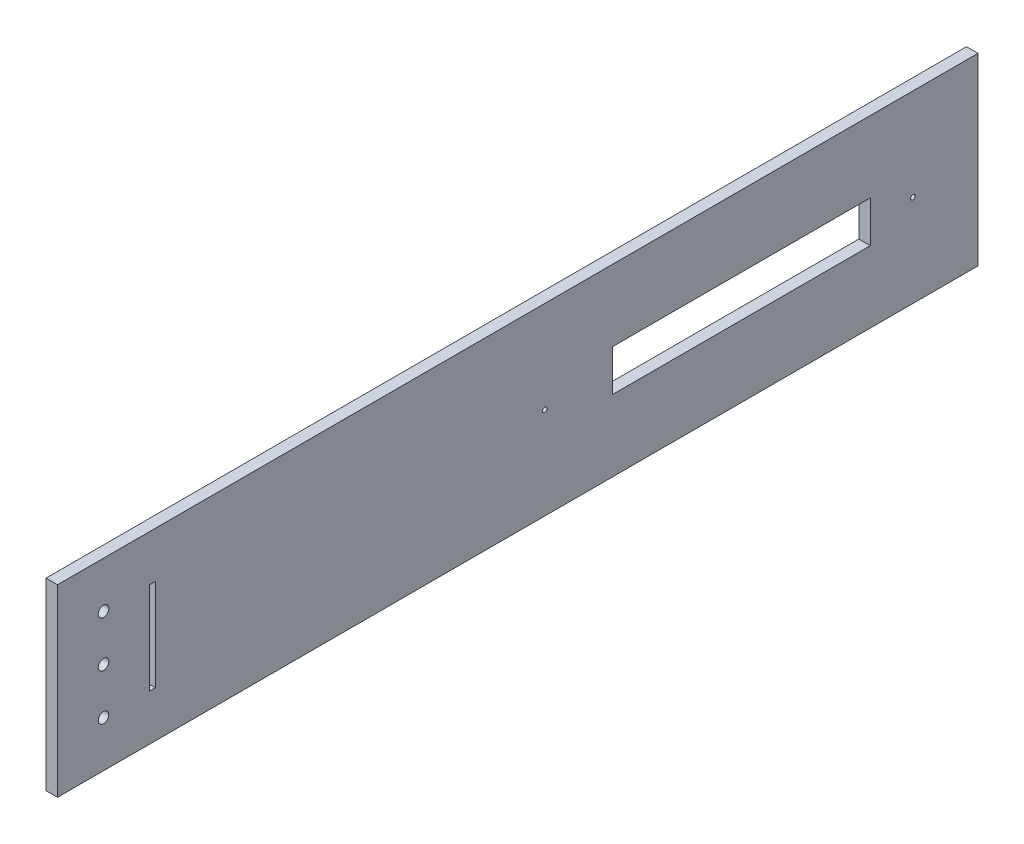
SolidWorks part; units mm, degrees
ref_plane "Front Plane" through (0, 0, 0) normal (0, 0, 1) x (1, 0, 0)
ref_plane "Top Plane" through (0, 0, 0) normal (0, 1, 0) x (1, 0, 0)
ref_plane "Right Plane" through (0, 0, 0) normal (1, 0, 0) x (0, 0, -1)
sketch "Sketch1" plane through (0, 0, 0) normal (1, 0, 0) x (0, 0, -1)
  line L0 (0, 0) -> (-254, 0) construction
  line L1 (0, 25.4) -> (-254, 25.4)
  line L2 (0, 25.4) -> (0, -25.4)
  line L3 (0, -25.4) -> (-254, -25.4)
  line L4 (-254, 25.4) -> (-254, -25.4)
  line L5 (-100.838, 5.715) -> (-29.718, 5.715) construction
  line L6 (-29.718, 5.715) -> (-100.8721, 5.715)
  line L7 (-29.718, 5.715) -> (-29.718, -5.715)
  line L8 (-29.718, -5.715) -> (-100.8721, -5.715)
  line L9 (-100.8721, 5.715) -> (-100.8721, -5.715)
  line L10 (-32.3851, -5.715) -> (-100.8721, -5.715) construction
  line L11 (-227.0125, 0) -> (-228.6, 0) construction
  line L12 (-227.0125, 12.7) -> (-228.6, 12.7)
  line L13 (-227.0125, 12.7) -> (-227.0125, -12.7)
  line L14 (-227.0125, -12.7) -> (-228.6, -12.7)
  line L15 (-228.6, 12.7) -> (-228.6, -12.7)
  line L16 (-241.3, 12.7) -> (-241.3, -12.7) construction
  line L17 (-215.9, -139.7) -> (-215.9, 139.7) construction
  line L18 (-29.718, 5.715) -> (-29.718, -5.715) construction
  line L19 (-100.8721, -5.715) -> (-100.8721, 5.715) construction
  circle A0 centre (-17.9578, 0) radius 0.635
  circle A1 centre (-119.5578, 0) radius 0.635
  circle A2 centre (-119.5578, 0) radius 0.635 construction
  circle A3 centre (-17.9578, 0) radius 0.635 construction
  circle A4 centre (-241.3, 0) radius 1.4605
  circle A5 centre (-241.3, 12.7) radius 1.4605
  circle A8 centre (-241.3, -12.7) radius 1.4605
  dimension "D6" = 2.921
  dimension "D7" = 2.921
  dimension "D8" = 38.1
  dimension "D10" = 2.921
  dimension "D1" = 50.8
  dimension "D2" = 25.4
  dimension "D3" = 1.5875
  dimension "D4" = 25.4
  dimension "D5" = 12.7
extrude "Boss-Extrude1" add sketch "Sketch1" against normal blind 3.175
equation "\"D6@Sketch1\"=\"D7@Sketch1\""
equation "\"D10@Sketch1\"=\"D7@Sketch1\""
